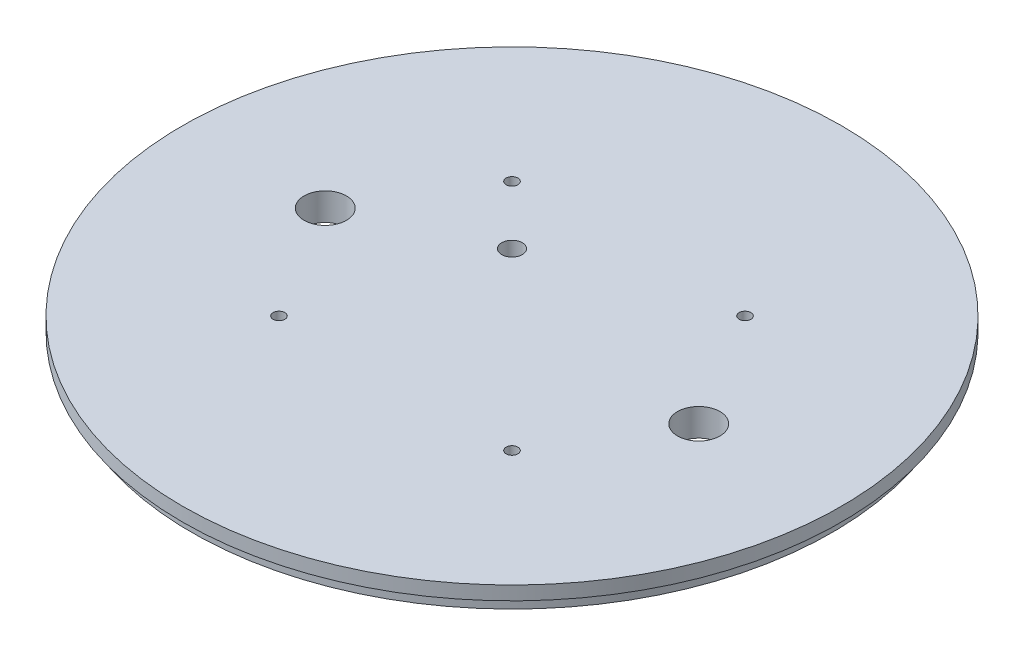
SolidWorks part; units mm, degrees
material "6061-T6 (SS)"
ref_plane "Front Plane" through (0, 0, 0) normal (0, 0, 1) x (1, 0, 0)
ref_plane "Top Plane" through (0, 0, 0) normal (0, 1, 0) x (1, 0, 0)
ref_plane "Right Plane" through (0, 0, 0) normal (1, 0, 0) x (0, 0, -1)
sketch "Sketch1" plane through (0, 0, 0) normal (0, 1, 0) x (1, 0, 0)
  line L0 (0, -76.2) -> (0, 76.2) construction
  line L1 (-76.2, 0) -> (76.2, 0) construction
  line L2 (-26.9408, 26.9408) -> (0, 0) construction
  line L3 (0, 56.7387) -> (0, 29.6936) construction
  line L4 (3.6407, 56.7387) -> (3.6407, 29.6936) construction
  line L5 (-3.6407, 56.7387) -> (-3.6407, 29.6936) construction
  line L6 (0, -56.7387) -> (0, -29.6936) construction
  line L7 (3.6407, -56.7387) -> (3.6407, -29.6936) construction
  line L8 (-3.6407, -56.7387) -> (-3.6407, -29.6936) construction
  line L9 (-53.8815, -53.8815) -> (54.3236, 54.3236) construction
  circle A0 centre (0, 0) radius 76.2
  circle A1 centre (0, 0) radius 3.175 construction
  circle A2 centre (43.18, 0) radius 4.9022
  circle A3 centre (-43.18, 0) radius 4.9022
  circle A4 centre (-26.9408, 26.9408) radius 1.3589
  arc A6 (3.6407, 56.7387) -> (-3.6407, 56.7387) centre (0, 56.7387) ccw construction
  arc A7 (-3.6407, 29.6936) -> (3.6407, 29.6936) centre (0, 29.6936) ccw construction
  arc A8 (3.6407, -56.7387) -> (-3.6407, -56.7387) centre (0, -56.7387) cw construction
  arc A9 (-3.6407, -29.6936) -> (3.6407, -29.6936) centre (0, -29.6936) cw construction
  circle A10 centre (26.9408, -26.9408) radius 1.3589
  circle A11 centre (-13.4704, 13.4704) radius 2.3813
  circle A12 centre (-26.9408, -26.9408) radius 1.3589
  circle A13 centre (26.9408, 26.9408) radius 1.3589
  circle A14 centre (-26.9408, 26.9408) radius 1.3589
  circle A15 centre (26.9408, -26.9408) radius 1.3589
  circle A16 centre (26.9408, 26.9408) radius 1.3589
  circle A17 centre (-26.9408, -26.9408) radius 1.3589
  point P16 (0, 43.2162)
  point P19 (0, 0)
  point P26 (0, -43.2162)
  point P50 (0, 0)
  dimension "D1" = 152.4
  dimension "D2" = 6.35
  dimension "D3" = 9.8044
  dimension "D5" = 2.7178
  dimension "D8" = 4.7625
  dimension "D6" = 38.1
  dimension "D7" = 45
  dimension "D4" = 45
  dimension "D9" = 43.18
  dimension "D10" = 4
extrude "Boss-Extrude1" add sketch "Sketch1" along normal blind 6.35 contours A0 A13 A10 A4 A2 A3 A11 A12 region at (0.0133, 0, 0.0133)
sketch "Sketch2" plane through (0, 0, 0) normal (0, -1, 0) x (1, 0, 0)
  circle A0 centre (0, 0) radius 76.2
  circle A1 centre (0, 0) radius 74.041
  dimension "D1" = 152.4
  dimension "D2" = 148.082
extrude "Cut-Extrude1" cut sketch "Sketch2" against normal blind 3.175
sketch "Sketch3" plane through (0, 6.35, 0) normal (0, 1, 0) x (1, 0, 0)
  line L0 (0, 76.2) -> (0, -76.2) construction
  line L1 (-76.2, 0) -> (76.2, 0) construction
  line L2 (0, 34.798) -> (0, 13.97) construction
  line L3 (3.2385, 34.798) -> (3.2385, 13.97)
  line L4 (-3.2385, 34.798) -> (-3.2385, 13.97)
  line L5 (0, -34.798) -> (0, -13.97) construction
  line L6 (3.2385, -34.798) -> (3.2385, -13.97)
  line L7 (-3.2385, -34.798) -> (-3.2385, -13.97)
  arc A1 (3.2385, 34.798) -> (-3.2385, 34.798) centre (0, 34.798) ccw
  arc A2 (-3.2385, 13.97) -> (3.2385, 13.97) centre (0, 13.97) ccw
  arc A3 (3.2385, -34.798) -> (-3.2385, -34.798) centre (0, -34.798) cw
  arc A4 (-3.2385, -13.97) -> (3.2385, -13.97) centre (0, -13.97) cw
  point P7 (0, 13.97)
  point P8 (0, 34.798)
  point P12 (0, 24.384)
  point P20 (0, -24.384)
  point P25 (0, -34.798)
  point P26 (0, -13.97)
  dimension "D1" = 13.97
  dimension "D2" = 20.828
  dimension "D3" = 6.477
extrude "Cut-Extrude2" cut sketch "Sketch3" against normal blind 3.556 from offset 3.175 offset against normal yes
equation "\"leadDist\"=1.5"
equation "\"Lead_Screw_Dist\"= 3.4in"
equation "\"Lead_Screw_Diam\"= 0.386in"
equation "\"D3@Sketch1\"=\"Lead_Screw_Diam\""
equation "\"D9@Sketch1\"=\"Lead_Screw_Dist\"/2"
